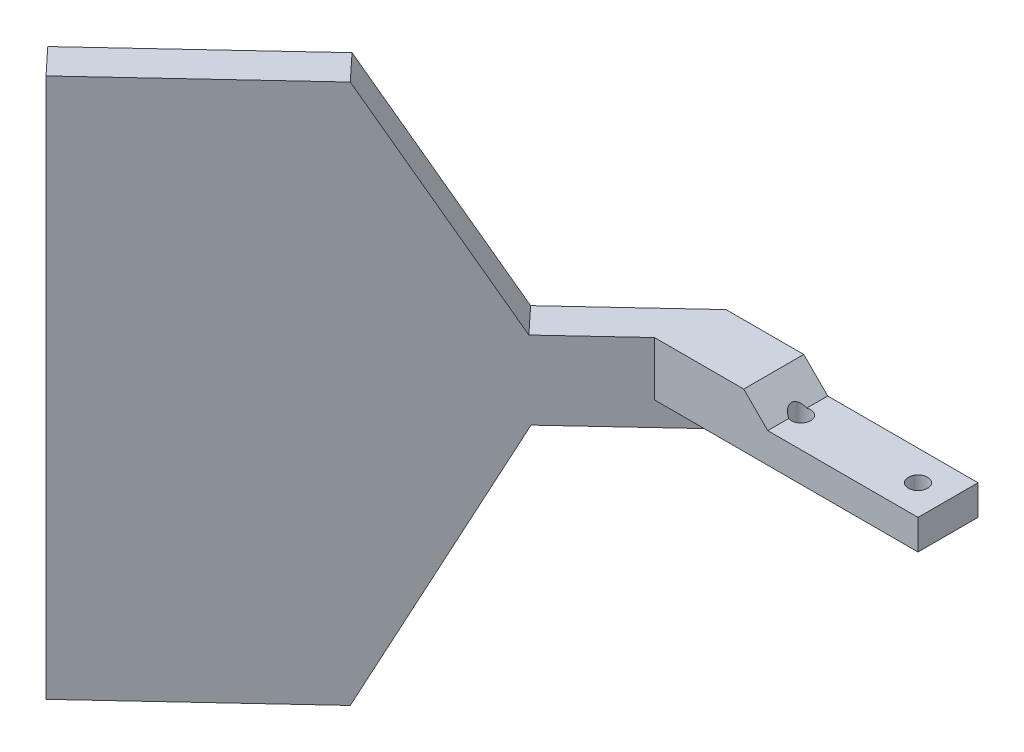
SolidWorks part; units mm, degrees
ref_plane "Front" through (0, 0, 0) normal (0, 0, 1) x (1, 0, 0)
ref_plane "Top" through (0, 0, 0) normal (0, 1, 0) x (1, 0, 0)
ref_plane "Right" through (0, 0, 0) normal (1, 0, 0) x (0, 0, -1)
sketch "Sketch1" plane through (0, 0, 0) normal (0, 1, 0) x (1, 0, 0)
  line L0 (0, 10) -> (0, 0)
  line L1 (0, 0) -> (42, 0)
  line L3 (0, 10) -> (42, 10)
  line L4 (42, 0) -> (42, 10)
  line L9 (0, 10) -> (-58.5083, -44.5599)
  line L10 (-58.5083, -44.5599) -> (-54.4163, -48.948)
  line L11 (0, 10) -> (4.092, 5.6119)
  line L12 (-54.4163, -48.948) -> (4.092, 5.6119)
  line L13 (0, 0) -> (-1.926, 0)
  line L14 (-1.926, 0) -> (0, 1.796)
  line L15 (0, 1.796) -> (0, 0)
  dimension "D1" = 10
  dimension "D2" = 42
  dimension "D3" = 223
  dimension "D4" = 80
  dimension "D5" = 6
  dimension "D6" = 270
extrude "Boss-Extrude1" add sketch "Sketch1" along normal blind 5 contours L10 L12 L1 L0 L9 | L1 L12 L11 L0 | L12 L1 L4 L3 L11 | L13 L0 L12 region at (1.364, 0, -5.8026) region at (-28.2435, 0, 20.3899) region at (21.8174, 0, -4.9666) region at (-0.642, 0, -0.5987)
sketch "Sketch3" plane through (0, 5, 0) normal (0, 1, 0) x (1, 0, 0)
  line L0 (-58.5083, -44.5599) -> (-54.4163, -48.948)
  line L1 (-54.4163, -48.948) -> (-28.1712, -24.474)
  line L2 (-54.4163, -48.948) -> (-1.926, 0) construction
  line L3 (-28.1712, -24.474) -> (-32.2631, -20.0859)
  line L4 (0, 10) -> (-58.5083, -44.5599) construction
  line L5 (-32.2631, -20.0859) -> (-58.5083, -44.5599)
extrude "Boss-Extrude2" add sketch "Sketch3" along normal blind 40
sketch "Sketch4" plane through (0, 0, 0) normal (0, -1, 0) x (1, 0, 0)
  line L0 (-58.5083, 44.5599) -> (-54.4163, 48.948)
  line L1 (-54.4163, 48.948) -> (-28.1712, 24.474)
  line L2 (-54.4163, 48.948) -> (-1.926, 0) construction
  line L3 (-28.1712, 24.474) -> (-32.2631, 20.0859)
  line L4 (0, -10) -> (-58.5083, 44.5599) construction
  line L5 (-32.2631, 20.0859) -> (-58.5083, 44.5599)
extrude "Boss-Extrude3" add sketch "Sketch4" along normal blind 45
sketch "Sketch5" plane through (-4.9878, 0, -5.3488) normal (-0.682, 0, -0.7314) x (-0.7314, 0, 0.682)
  line L0 (37.2943, -45) -> (37.2943, 0)
  line L1 (37.2943, 0) -> (13.889, 0)
  line L2 (-6.82, 0) -> (37.2943, 0) construction
  line L3 (13.889, 0) -> (37.2943, -45)
  line L4 (13.889, 5) -> (37.2943, 45)
  line L5 (-6.82, 5) -> (37.2943, 5) construction
  line L6 (37.2943, 45) -> (37.2943, 5)
  line L7 (37.2943, 5) -> (13.889, 5)
extrude "Boss-Extrude4" add sketch "Sketch5" against normal blind 6
sketch "Sketch8" plane through (0, 0, 0) normal (0, -1, 0) x (1, 0, 0)
  line L0 (0, -10) -> (-23.7044, 12.1047)
  line L1 (-32.2631, 20.0859) -> (-15.1456, 4.1235) construction
  line L6 (-23.7044, 12.1047) -> (-19.6124, 16.4928)
  line L7 (-28.1712, 24.474) -> (-11.0536, 8.5116) construction
  line L8 (-19.6124, 16.4928) -> (8.7977, -10)
  line L9 (0, -10) -> (42, -10) construction
  line L10 (8.7977, -10) -> (0, -10)
extrude "Boss-Extrude6" add sketch "Sketch8" along normal blind 4
sketch "Sketch9" plane through (0, 5, 0) normal (0, 1, 0) x (1, 0, 0)
  line L3 (-16.6671, -5.5424) -> (-32.2631, -20.0859) construction
  line L4 (-24.4651, -12.8141) -> (0, 10)
  line L6 (-24.4651, -12.8141) -> (-16.7996, -13.8699)
  line L7 (-28.1712, -24.474) -> (-11.0536, -8.5116) construction
  line L9 (-16.7996, -13.8699) -> (8.7977, 10)
  line L10 (0, 10) -> (42, 10) construction
  line L11 (8.7977, 10) -> (0, 10)
  line L12 (42, 0) -> (-1.926, 0) construction
  line L13 (8.7977, 0) -> (-1.926, 0)
  line L14 (-1.926, 0) -> (8.7977, 10)
  line L15 (8.7977, 10) -> (17.9505, 10)
  line L16 (17.9505, 10) -> (17.9505, 0)
  line L17 (17.9505, 0) -> (8.7977, 0)
  line M1 (-15.1456, -4.1235) -> (-11.0536, -8.5116)
  line M2 (-11.0536, -8.5116) -> (-1.926, 0)
  line M3 (-1.926, 0) -> (42, 0)
  line M6 (42, 10) -> (0, 10)
  line M7 (0, 10) -> (-15.1456, -4.1235)
extrude "Boss-Extrude7" add sketch "Sketch9" along normal blind 4 contours L9 M3 | L9 M2 M6 M7 M1 | L6 L9 L4 M1 region at (-17.0984, 5, 9.7222) region at (-4.2059, 5, -1.7921) region at (10.3631, 5, -4.3843)
fillet "Fillet2" [suppressed] radius 15
fillet "Fillet7" radius 5 1 edges at (17.9505, 9, -5) profile chamfer
sketch "Sketch11" plane through (0, 0, 0) normal (0, -1, 0) x (-1, 0, 0)
  circle A0 centre (-17.5, 5) radius 1.6
extrude "Cut-Extrude2" cut sketch "Sketch11" against normal blind 10
sketch "Sketch13" plane through (0, 5, 0) normal (0, 1, 0) x (1, 0, 0)
  circle A0 centre (37, 5) radius 1.6
extrude "Cut-Extrude4" cut sketch "Sketch13" against normal blind 10
